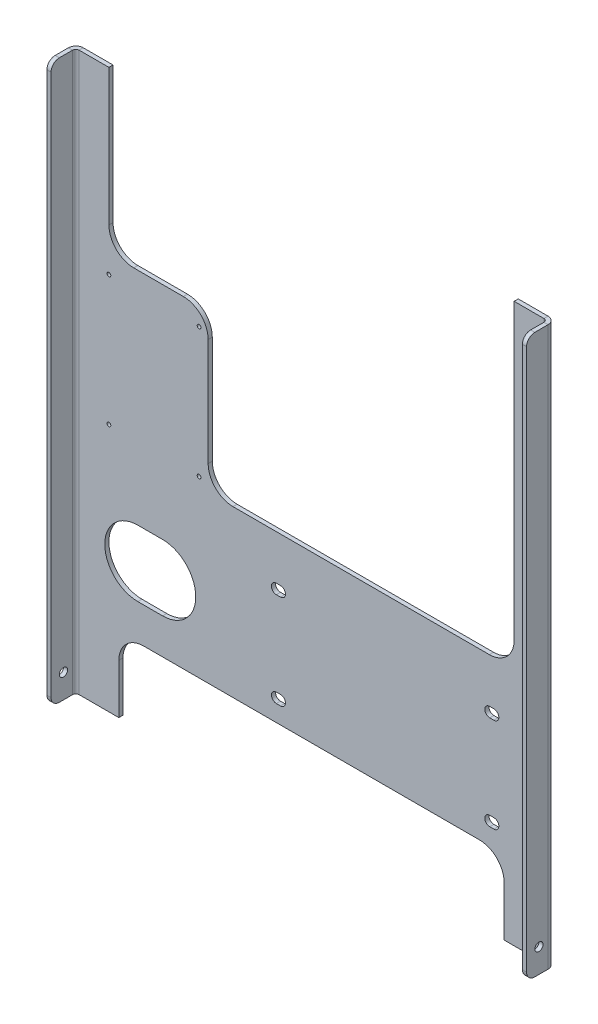
SolidWorks part; units mm, degrees
note: The reader was unsure of these and kept them because the rebuilt part matched: flange length of "边线-法兰1".
material "Q355"
ref_plane "前视基准面" through (0, 0, 0) normal (0, 0, 1) x (1, 0, 0)
ref_plane "上视基准面" through (0, 0, 0) normal (0, 1, 0) x (1, 0, 0)
ref_plane "右视基准面" through (0, 0, 0) normal (1, 0, 0) x (0, 0, -1)
sketch "草图1" plane through (0, 0, 0) normal (0, 0, 1) x (1, 0, 0)
  line L2 (0, 0) -> (0, 675)
  line L3 (0, 675) -> (45, 675)
  line L4 (45, 675) -> (45, 480)
  line L5 (45, 480) -> (165, 480)
  line L6 (165, 480) -> (165, 290)
  line L7 (165, 290) -> (535, 290)
  line L8 (535, 290) -> (535, 675)
  line L9 (535, 675) -> (580, 675)
  line L10 (580, 675) -> (580, 0)
  line L13 (580, 0) -> (523, 0)
  line L14 (57, 0) -> (57, 90)
  line L15 (57, 90) -> (523, 90)
  line L16 (523, 90) -> (523, 0)
  line L17 (57, 0) -> (0, 0)
  line L18 (154, 458) -> (45, 458) construction
  line L19 (154, 458) -> (154, 301) construction
  line L20 (45, 458) -> (45, 301) construction
  line L21 (154, 301) -> (45, 301) construction
  line L22 (80, 173) -> (110, 173) construction
  line L23 (80, 133) -> (110, 133)
  line L24 (80, 213) -> (110, 213)
  circle A1 centre (154, 458) radius 2.25
  circle A3 centre (45, 458) radius 2.25
  circle A4 centre (154, 301) radius 2.25
  circle A5 centre (45, 301) radius 2.25
  arc A6 (80, 213) -> (80, 133) centre (80, 173) ccw
  arc A7 (110, 133) -> (110, 213) centre (110, 173) ccw
  dimension "D19" = 4.5
  dimension "D22" = 4.5
  dimension "D25" = 4.5
  dimension "D26" = 4.5
  dimension "D27" = 80
  dimension "D28" = 30
  dimension "D7" = 80
  dimension "D2" = 90
  dimension "D4" = 466
  dimension "D5" = 675
  dimension "D6" = 580
  dimension "D9" = 45
  dimension "D10" = 195
  dimension "D11" = 190
  dimension "D12" = 370
  dimension "D13" = 385
  dimension "D20" = 11
  dimension "D21" = 22
  dimension "D23" = 109
  dimension "D24" = 157
  dimension "D29" = 83
base flange "基体-法兰1" sketch "草图1" thickness 5 reverse thickness direction no parameters "D1"=4
fillet "圆角1" radius 30 6 edges at (57, 90, -2.5) (523, 90, -2.5) (535, 290, -2.5) (165, 290, -2.5) (165, 480, -2.5) (45, 480, -2.5)
edge flange "边线-法兰1" sketch "草图9" flange profiles "草图9", "草图10" flange angle 90 flange length 35 flange position material inside bend radius 4 thickness 5 relief rectangular parameters "D6"=10, "D8"=1
sketch "草图9" plane through (0, 0, 0) normal (-1, 0, 0) x (0, -1, 0)
  line L2 (-675, 0) -> (-675, 30)
  line L3 (-675, 30) -> (0, 30)
  line L4 (0, 30) -> (0, 0)
  line L7 (-675, 0) -> (0, 0) construction
  line L8 (-675, 0) -> (0, 0)
sketch "草图10" plane through (580, 0, 0) normal (1, 0, 0) x (0, 1, 0)
  line L0 (0, 0) -> (675, 0) construction
  line L1 (0, 0) -> (675, 0)
  line L2 (0, 0) -> (0, 30)
  line L3 (0, 30) -> (675, 30)
  line L4 (675, 30) -> (675, 0)
bend "边线折弯1" bend radius 4 bend angle 90 parameters "D5"=1
bend "边线折弯2" bend radius 4 bend angle 90 parameters "D5"=2
sketch "草图11" plane through (0, 0, 0) normal (0, 0, 1) x (1, 0, 0)
  line L0 (252.5, 116) -> (247.5, 116) construction
  line L5 (252.5, 110) -> (247.5, 110)
  line L6 (252.5, 122) -> (247.5, 122)
  line L7 (510.5, 116) -> (505.5, 116) construction
  line L10 (510.5, 110) -> (505.5, 110)
  line L13 (510.5, 122) -> (505.5, 122)
  line L16 (250, 230) -> (250, 116) construction
  line L21 (250, 173) -> (508, 173) construction
  line L22 (508, 230) -> (508, 116) construction
  line L23 (510.5, 230) -> (505.5, 230) construction
  line L24 (510.5, 224) -> (505.5, 224)
  line L25 (510.5, 236) -> (505.5, 236)
  line L26 (252.5, 230) -> (247.5, 230) construction
  line L27 (252.5, 224) -> (247.5, 224)
  line L28 (252.5, 236) -> (247.5, 236)
  line L29 (505, 290) -> (195, 290) construction
  line L30 (165, 320) -> (165, 450) construction
  line L31 (250, 46) -> (508, 46) construction
  line L32 (250, 46) -> (490.0067, 46) construction
  line L33 (250, 173) -> (490.0067, 173) construction
  arc A0 (252.5, 110) -> (252.5, 122) centre (252.5, 116) ccw
  arc A1 (247.5, 122) -> (247.5, 110) centre (247.5, 116) ccw
  arc A8 (510.5, 110) -> (510.5, 122) centre (510.5, 116) ccw
  arc A9 (505.5, 122) -> (505.5, 110) centre (505.5, 116) ccw
  arc A10 (510.5, 224) -> (510.5, 236) centre (510.5, 230) ccw
  arc A11 (505.5, 236) -> (505.5, 224) centre (505.5, 230) ccw
  arc A12 (252.5, 224) -> (252.5, 236) centre (252.5, 230) ccw
  arc A13 (247.5, 236) -> (247.5, 224) centre (247.5, 230) ccw
  circle A14 centre (379, 46) radius 15 construction
  point P2 (250, 116)
  point P12 (508, 116)
  point P19 (508, 230)
  point P26 (250, 230)
  dimension "D1" = 2
  dimension "D9" = 127
  dimension "D5" = 6
  dimension "D8" = 5
  dimension "D10" = 30
  dimension "D2" = 2
  dimension "D3" = 60
  dimension "D4" = 85
  dimension "D6" = 258
  dimension "D7" = 114
extrude "切除-拉伸3" cut sketch "草图11" against normal up to next
fillet "圆角2" radius 10 4 edges at (2.5, 675, 30) (577.5, 675, 30) (577.5, 0, 30) (2.5, 0, 30)
sketch "草图12" plane through (580, 0, 0) normal (1, 0, 0) x (0, 0, -1)
  line L1 (-30, 665) -> (-30, 10) construction
  line L2 (-20, 0) -> (-4, 0) construction
  circle A0 centre (-15, 29) radius 5
  dimension "D1" = 10
  dimension "D2" = 29
  dimension "D3" = 15
extrude "切除-拉伸4" cut sketch "草图12" against normal through all
sketch "折弯-线1" [suppressed] plane through (0, 0, 0) normal (0, 1, 0) x (1, 0, 0)
sketch "边界框1" [suppressed] plane through (0, 0, 0) normal (0, 1, 0) x (1, 0, 0)
sheet metal parameters "钣金6" thickness 5 parameters "D1"=4
flat pattern "平板型式6" [suppressed]
sketch "折弯-线2" plane through (0, 0, 0) normal (0, 1, 0) x (1, 0, 0)
sketch3d "边界框2" [suppressed]
  line L0 (620, 675, 0) -> (620, 0, 0) construction
  line L1 (0, 675, 0) -> (0, 0, 0) construction
  line L2 (620, 675, 0) -> (0, 675, 0) construction
  line L3 (620, 0, 0) -> (0, 0, 0) construction
sheet metal parameters "钣金15" thickness 5 parameters "D1"=4
flat pattern "平板型式6" [suppressed]
sketch "折弯-线2" plane through (0, 0, 0) normal (0, 1, 0) x (1, 0, 0)
sketch3d "边界框2" [suppressed]
  line L0 (620, 675, 0) -> (620, 0, 0) construction
  line L1 (0, 675, 0) -> (0, 0, 0) construction
  line L2 (620, 675, 0) -> (0, 675, 0) construction
  line L3 (620, 0, 0) -> (0, 0, 0) construction
bend of the flat pattern "展开-<边线折弯1>1"
bend of the flat pattern "展开-<边线折弯2>1"
sheet metal parameters "钣金16" thickness 5 parameters "D1"=4
flat pattern "平板型式6" [suppressed]
sketch "折弯-线2" plane through (0, 0, 0) normal (0, 1, 0) x (1, 0, 0)
sketch3d "边界框2" [suppressed]
  line L0 (620, 675, 0) -> (620, 0, 0) construction
  line L1 (0, 675, 0) -> (0, 0, 0) construction
  line L2 (620, 675, 0) -> (0, 675, 0) construction
  line L3 (620, 0, 0) -> (0, 0, 0) construction
bend of the flat pattern "展开-<边线折弯1>1"
bend of the flat pattern "展开-<边线折弯2>1"
sheet metal parameters "钣金17" thickness 5 parameters "D1"=4
flat pattern "平板型式6"
sketch "折弯-线2" plane through (0, 0, 0) normal (0, 0, 1) x (1, 0, 0)
  line L0 (576.1051, 0) -> (576.1051, 675) construction
  line L1 (3.8949, 675) -> (3.8949, 0) construction
  line L2 (576.1051, 0) -> (576.1051, 675) construction
  line L3 (3.8949, 675) -> (3.8949, 0) construction
sketch3d "边界框2" [suppressed]
  line L0 (607.2102, 0, 0) -> (607.2102, 675, 0) construction
  line L1 (-27.2102, 0, 0) -> (-27.2102, 675, 0) construction
  line L2 (607.2102, 0, 0) -> (-27.2102, 0, 0) construction
  line L3 (607.2102, 675, 0) -> (-27.2102, 675, 0) construction
bend of the flat pattern "展开-<边线折弯1>1"
bend of the flat pattern "展开-<边线折弯2>1"
